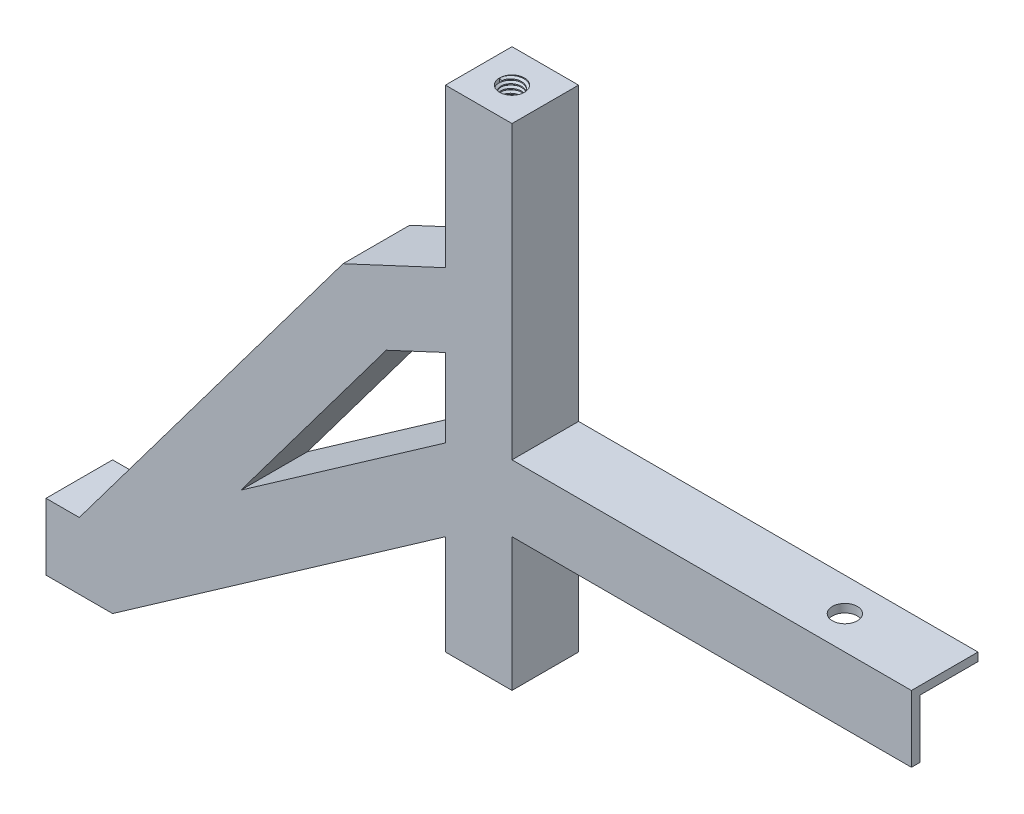
SolidWorks part; units mm, degrees
material "Plain Carbon Steel"
ref_plane "Front Plane" through (0, 0, 0) normal (0, 0, 1) x (1, 0, 0)
ref_plane "Top Plane" through (0, 0, 0) normal (0, 1, 0) x (1, 0, 0)
ref_plane "Right Plane" through (0, 0, 0) normal (1, 0, 0) x (0, 0, -1)
sketch "Sketch1" plane through (0, 0, 0) normal (0, 1, 0) x (1, 0, 0)
  line L1 (12.7, -12.7) -> (-12.7, -12.7)
  line L2 (12.7, -12.7) -> (12.7, 12.7)
  line L3 (12.7, 12.7) -> (-12.7, 12.7)
  line L4 (-12.7, -12.7) -> (-12.7, 12.7)
  line L5 (12.7, -12.7) -> (-12.7, 12.7) construction
  line L6 (12.7, 12.7) -> (-12.7, -12.7) construction
  line L7 (10.16, -10.16) -> (-10.16, -10.16)
  line L8 (10.16, -10.16) -> (10.16, 10.16)
  line L9 (10.16, 10.16) -> (-10.16, 10.16)
  line L10 (-10.16, -10.16) -> (-10.16, 10.16)
  line L11 (10.16, -10.16) -> (-10.16, 10.16) construction
  line L12 (10.16, 10.16) -> (-10.16, -10.16) construction
  point P0 (0, 0)
  point P5 (0, 0)
  dimension "D1" = 2.54
  dimension "1" = 25.4
extrude "Sq_Tb Extrude" add sketch "Sketch1" along normal blind 187.325
sketch "Sketch3" plane through (0, 187.325, 0) normal (0, 1, 0) x (1, 0, 0)
  line L1 (10.16, -10.16) -> (-10.16, -10.16)
  line L2 (10.16, -10.16) -> (10.16, 10.16)
  line L3 (10.16, 10.16) -> (-10.16, 10.16)
  line L4 (-10.16, -10.16) -> (-10.16, 10.16)
  line L5 (10.16, -10.16) -> (-10.16, 10.16) construction
  line L6 (10.16, 10.16) -> (-10.16, -10.16) construction
  circle A0 centre (0, 0) radius 4.7625
  point P0 (0, 0)
  dimension "D1" = 9.525
extrude "End Caps" add sketch "Sketch3" against normal blind 6.35
ref_plane "Mid-Plane" through (0, 93.6625, 0) normal (0, 1, 0) x (1, 0, 0)
mirror "End Cap Mirror" about plane through (0, 93.6625, 0) normal (0, 1, 0) of "End Caps"
thread "Top Thread" pitch 1.5875 method extrude profile "Thread Profile1" start angle 0, offset 0, length 0, pitch 1.5875, diameter 9.525
ref_plane "Plane2" through (-4.7625, 187.325, 0) normal (0, 0, 1) x (-1, 0, 0)
sketch "Thread Profile1" plane through (-4.7625, 187.325, 0) normal (0, 0, 1) x (-1, 0, 0)
  line L0 (0, 0) -> (0, 1.5875) construction
  line L11 (0, 0) -> (0, 1.3891)
  line L12 (0, 1.3891) -> (-0.8593, 0.893)
  line L13 (-0.8593, 0.893) -> (-0.8593, 0.4961)
  line L15 (-0.8593, 0.4961) -> (0, 0)
  line L17 (-0.8593, 0.6945) -> (0, 0.6945) construction
  point P2 (0, 0)
  dimension "Pitch" = 1.5875
  dimension "Profile_Angle" = 60
  dimension "Profile_Land" = 0.3969
  dimension "Profile_Height" = 0.8593
thread "Bottom Thread" pitch 1.5875 method extrude profile "Thread Profile2" start angle 0, offset 0, length 0, pitch 1.5875, diameter 9.525
ref_plane "Plane3" through (4.7625, 0, 0) normal (0, 0, 1) x (1, 0, 0)
sketch "Thread Profile2" plane through (4.7625, 0, 0) normal (0, 0, 1) x (1, 0, 0)
  line L0 (0, 0) -> (0, 1.5875) construction
  line L11 (0, 0) -> (0, 1.3891)
  line L12 (0, 1.3891) -> (-0.8593, 0.893)
  line L13 (-0.8593, 0.893) -> (-0.8593, 0.4961)
  line L15 (-0.8593, 0.4961) -> (0, 0)
  line L17 (-0.8593, 0.6945) -> (0, 0.6945) construction
  point P2 (0, 0)
  dimension "Pitch" = 1.5875
  dimension "Profile_Angle" = 60
  dimension "Profile_Land" = 0.3969
  dimension "Profile_Height" = 0.8593
sketch "Sketch9" plane through (0, 0, 0) normal (0, 0, 1) x (1, 0, 0)
  line L0 (-12.7, 126.996) -> (-51.7653, 108.7796)
  line L1 (-12.7, 187.325) -> (-12.7, 0) construction
  line L2 (-102.0827, 41.6898) -> (-81.7627, 26.4498) construction
  line L3 (-35.2635, 88.4487) -> (-12.7, 98.9702)
  line L4 (-12.7, 38.0909) -> (-139.7, -50.8)
  line L5 (-90.7525, 14.4633) -> (-12.7, 69.0945)
  line L6 (-12.7, 69.0945) -> (-12.7, 38.0909)
  line L8 (-51.7653, 108.7796) -> (-152.4, -25.4)
  line L9 (-12.7, 126.996) -> (-12.7, 98.9702)
  line L10 (-139.7, -50.8) -> (-35.2635, 88.4487)
  line L11 (-139.7, -50.8) -> (-165.1, -50.8)
  line L12 (-165.1, -50.8) -> (-165.1, -25.4)
  line L13 (-165.1, -25.4) -> (-152.4, -25.4)
  line L14 (-32.2327, 117.8878) -> (-21.4982, 94.8676) construction
  line L15 (-165.1, -38.1) -> (0, -38.1) construction
  line L16 (0, -38.1) -> (0, 0) construction
  line L18 (-12.7, 0) -> (12.7, 0) construction
  line L19 (-51.7262, 41.7789) -> (-37.1613, 20.9697) construction
  line L20 (-12.7, 69.0945) -> (32.9312, 3.9003) construction
  line L21 (-139.7, -50.8) -> (-114.9192, -86.2048) construction
  dimension "D3" = 172.7962
  dimension "D1" = 25.4
  dimension "D2" = 43.1038
  dimension "D4" = 65
  dimension "D5" = 12.7
  dimension "D6" = 152.4
  dimension "D7" = 115
  dimension "D8" = 25.4
  dimension "D9" = 50.8
  dimension "D10" = 55.011
  dimension "D11" = 60.329
  dimension "D12" = 38.0909
  dimension "D13" = 88.9052
extrude "Sq_Tb Angles" add sketch "Sketch9" along normal blind 12.7 and the other way blind 12.7 contours L13 L12 L11 L10 L3 L9 L0 L8 | L10 L4 L6 L5
sketch "Sketch11" plane through (0, 0, 0) normal (0, 0, 1) x (1, 0, 0)
  line L0 (-165.1, -38.1) -> (-254, -38.1)
  line L1 (-165.1, -50.8) -> (-165.1, -25.4) construction
  line L2 (-254, -38.1) -> (-254, -28.575)
  line L3 (-254, -28.575) -> (-165.1, -28.575)
  line L6 (-165.1, -28.575) -> (-165.1, -38.1)
  dimension "D2" = 9.525
  dimension "D4" = 88.9
revolve "Wheel Rod" [suppressed] add sketch "Sketch11" angle 360 about L0
thread "Wheel Threads" [suppressed] pitch 1.5875 start angle 0, offset 0, length 25.4, pitch 1.5875, diameter 19.05
ref_plane "Plane4" through (-254, -38.1, -9.525) normal (0, -1, 0) x (0, 0, -1)
sketch "Thread Profile3" plane through (-254, -38.1, -9.525) normal (0, -1, 0) x (0, 0, -1)
  line L0 (0, 0) -> (0, 1.5875) construction
  line L11 (0, 0) -> (0, 1.3891)
  line L12 (0, 1.3891) -> (-0.8593, 0.893)
  line L13 (-0.8593, 0.893) -> (-0.8593, 0.4961)
  line L15 (-0.8593, 0.4961) -> (0, 0)
  line L17 (-0.8593, 0.6945) -> (0, 0.6945) construction
  point P2 (0, 0)
  dimension "Pitch" = 1.5875
  dimension "Profile_Angle" = 60
  dimension "Profile_Land" = 0.3969
  dimension "Profile_Height" = 0.8593
ref_plane "Tie-Rod Mount Plane" through (0, 34.925, 0) normal (0, 1, 0) x (1, 0, 0)
sketch "Sketch15" plane through (0, 34.925, 0) normal (0, 1, 0) x (1, 0, 0)
  line L0 (0, 12.7) -> (12.7, 25.4)
  line L1 (12.7, 12.7) -> (-12.7, 12.7) construction
  line L2 (12.7, 25.4) -> (76.2, 25.4)
  line L3 (0, -12.7) -> (12.7, -25.4)
  line L4 (-12.7, -12.7) -> (12.7, -12.7) construction
  line L5 (0, 12.7) -> (12.7, 12.7)
  line L6 (12.7, -12.7) -> (12.7, 12.7) construction
  line L7 (12.7, 12.7) -> (12.7, -12.7)
  line L8 (12.7, -12.7) -> (0, -12.7)
  line L9 (12.7, -25.4) -> (76.2, -25.4)
  line L10 (76.2, -25.4) -> (76.2, 25.4) construction
  line L11 (12.7, 25.4) -> (12.7, 12.7) construction
  line L12 (12.7, -12.7) -> (12.7, -25.4) construction
  line L13 (76.2, 25.4) -> (88.9, 12.7)
  line L14 (88.9, 12.7) -> (88.9, -12.7)
  line L15 (88.9, -12.7) -> (76.2, -25.4)
  line L16 (12.7, 0) -> (88.9, 0) construction
  dimension "D1" = 12.7
  dimension "D2" = 76.2
  dimension "D3" = 12.7
extrude "Tie-Rod Mount Plate" [suppressed] add sketch "Sketch15" along normal blind 6.35
sketch "Sketch16" [suppressed] plane through (0, 41.275, 0) normal (0, 1, 0) x (1, 0, 0)
  line L0 (12.7, 0) -> (63.5, 0) construction
  line L1 (12.7, -12.7) -> (12.7, 12.7) construction
  line L2 (63.5, 0) -> (63.5, 15.875) construction
  line L3 (12.7, 0) -> (76.2, 0) construction
  circle A0 centre (63.5, 15.875) radius 4.7625
  circle A1 centre (63.5, -15.875) radius 4.7625
  circle A2 centre (76.2, 0) radius 4.7625
  dimension "D1" = 50.8
  dimension "D3" = 9.525
  dimension "D2" = 15.875
  dimension "D4" = 63.5
extrude "Tie-Rod Mount Hole" [suppressed] cut sketch "Sketch16" against normal through all
ref_plane "Plane5" through (0, 50.8, 0) normal (0, -1, 0) x (-1, 0, 0)
sketch "Sketch17" plane through (0, 50.8, 0) normal (0, -1, 0) x (-1, 0, 0)
  line L0 (-12.7, -12.7) -> (-12.7, 12.7) construction
  line L1 (-12.7, 12.7) -> (12.7, 12.7)
  line L2 (-12.7, 12.7) -> (-12.7, 88.9)
  line L3 (-12.7, 88.9) -> (12.7, 88.9)
  line L4 (12.7, 12.7) -> (12.7, 88.9)
  line L5 (-12.7, 12.7) -> (12.7, 88.9) construction
  line L6 (-12.7, 88.9) -> (12.7, 12.7) construction
  line L7 (-12.7, 12.7) -> (12.7, 12.7) construction
  point P4 (0, 50.8)
  dimension "D1" = 25.4
  dimension "D2" = 76.2
extrude "Boss-Extrude1" [suppressed] add sketch "Sketch17" against normal blind 25.4
sketch "Sketch18" [suppressed] plane through (0, 76.2, 0) normal (0, 1, 0) x (1, 0, 0)
  line L0 (0, 0) -> (0, 63.5) construction
  circle A0 centre (0, 63.5) radius 4.7625
  dimension "D1" = 63.5
  dimension "D2" = 9.525
extrude "Cut-Extrude1" [suppressed] cut sketch "Sketch18" against normal through all
sketch "Sketch19" plane through (12.7, 0, 0) normal (1, 0, 0) x (0, 0, -1)
  line L0 (12.7, 76.2) -> (-12.7, 76.2)
  line L1 (-12.7, 187.325) -> (-12.7, 0) construction
  line L2 (-12.7, 76.2) -> (-12.7, 50.8)
  line L3 (-65.0506, 50.8) -> (65.0506, 50.8) construction
  line L4 (-12.7, 50.8) -> (-9.525, 50.8)
  line L5 (-9.525, 50.8) -> (-9.525, 73.025)
  line L6 (-9.525, 73.025) -> (12.7, 73.025)
  line L7 (12.7, 73.025) -> (12.7, 76.2)
  line L8 (-12.7, 0) -> (12.7, 0) construction
  dimension "D1" = 3.175
  dimension "D2" = 76.2
extrude "Boss-Extrude2" add sketch "Sketch19" along normal blind 152.4
sketch "Sketch20" plane through (0, 76.2, 0) normal (0, 1, 0) x (1, 0, 0)
  line L0 (88.9, -12.7) -> (88.9, 0) construction
  line L2 (165.1, -12.7) -> (12.7, -12.7) construction
  line L3 (0, 0) -> (31.75, 0) construction
  line L4 (31.75, 0) -> (127, 0) construction
  circle A0 centre (127, 0) radius 4.7625
  circle A1 centre (31.75, 0) radius 4.7625 construction
  point P8 (88.9, 0)
  dimension "D1" = 31.75
  dimension "D2" = 9.525
  dimension "D3" = 127
extrude "Cut-Extrude2" cut sketch "Sketch20" against normal through all
sketch "Sketch21" plane through (-165.1, 0, 0) normal (-1, 0, 0) x (0, 0, 1)
  circle A0 centre (0, -38.1) radius 9.525
  dimension "D1" = 19.05
extrude "Cut-Extrude3" cut sketch "Sketch21" against normal through all
